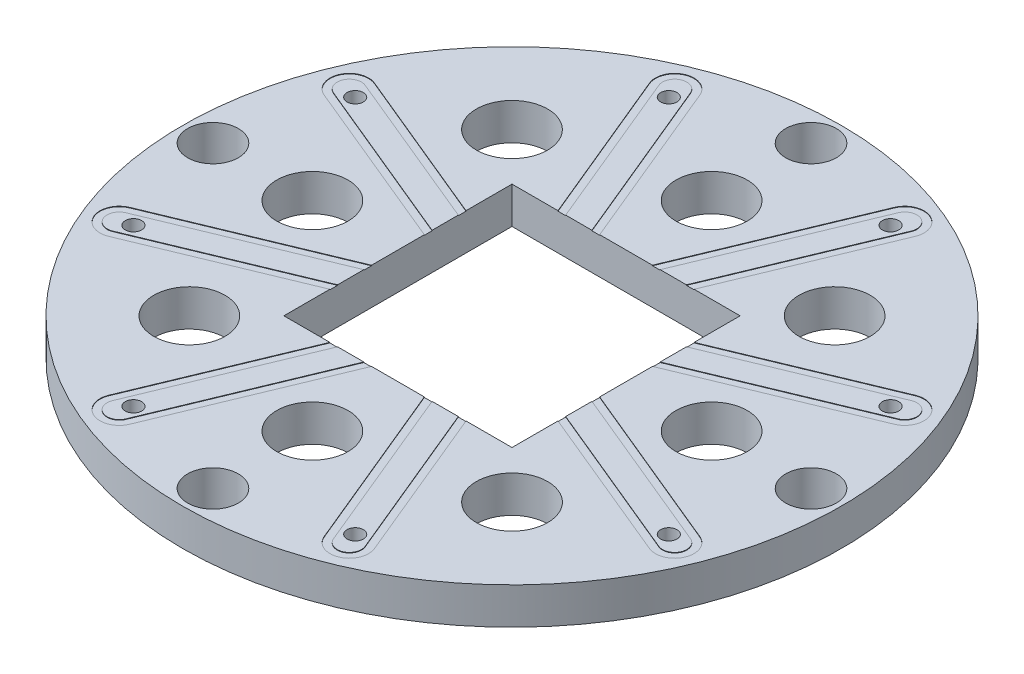
SolidWorks part; units mm, degrees
material "Ceramic Porcelain"
ref_plane "Front Plane" through (0, 0, 0) normal (0, 0, 1) x (1, 0, 0)
ref_plane "Top Plane" through (0, 0, 0) normal (0, 1, 0) x (1, 0, 0)
ref_plane "Right Plane" through (0, 0, 0) normal (1, 0, 0) x (0, 0, -1)
ref_axis "Y Axis" through (0, 0.0762, 0) along (0, -1, 0)
sketch "Boday Sketch" plane through (0, 0, 0) normal (0, 1, 0) x (1, 0, 0)
  circle A0 centre (0, 0) radius 11.557
  dimension "D1" = 23.114
extrude "Body" add sketch "Boday Sketch" against normal blind 1.27
sketch "Copper Sketch" plane through (0, 0, 0) normal (0, 1, 0) x (1, 0, 0)
  circle A0 centre (0, 0) radius 11.557
  dimension "D1" = 23.114
extrude "Copper" add sketch "Copper Sketch" along normal blind 0.0175
sketch "Screw Position" plane through (0, 0, 0) normal (0, 1, 0) x (1, 0, 0)
  point P0 (0, 10.541)
  dimension "D1" = 10.541
sketch "IO Hole Positions" plane through (0, 0, 0) normal (0, 1, 0) x (1, 0, 0)
  point P0 (-3.8881, 9.3866)
  point P1 (3.8881, 9.3866)
  point P5 (9.3866, 3.8881)
  point P6 (9.3866, -3.8881)
  point P7 (3.8881, -9.3866)
  point P8 (-3.8881, -9.3866)
  point P9 (-9.3866, -3.8881)
  point P10 (-9.3866, 3.8881)
  point P11 (0, 0)
  dimension "D2" = 8
sketch "Gap" plane through (0, 0, 0) normal (0, 1, 0) x (1, 0, 0)
  line L1 (0.6236, 0.2583) -> (-3.4102, 9.9969)
  line L2 (-4.6575, 9.4803) -> (-0.6236, -0.2583)
  line L3 (-0.6236, -0.2583) -> (0.6236, 0.2583)
  arc A0 (-3.4102, 9.9969) -> (-4.6575, 9.4803) centre (-4.0339, 9.7386) ccw
  point P0 (0.6236, 0.2583)
sketch "Center Sketch" plane through (0, 0, 0) normal (0, 1, 0) x (1, 0, 0)
  line L0 (0.3926, 0.1626) -> (-3.6412, 9.9013)
  line L1 (-4.4265, 9.576) -> (-0.3926, -0.1626)
  line L2 (-0.3926, -0.1626) -> (0.3926, 0.1626)
  arc A0 (-3.6412, 9.9013) -> (-4.4265, 9.576) centre (-4.0339, 9.7386) ccw
  point P0 (0.3926, 0.1626)
  point P3 (-3.6412, 9.9013)
  dimension "D1" = 0.425
hole_wizard "#0 Clearance Hole1" positions "Sketch23" profile "Sketch24" hole size "#0" standard "ANSI Inch" end condition through all
sketch "Sketch23" plane through (0, 0.0175, 0) normal (0, 1, 0) x (-1, 0, 0)
  point P0 (0, -10.4865)
sketch "Sketch24" plane through (0, 0.0175, -10.4865) normal (1, 0, 0) x (0, 0, 1)
  line L0 (0, 0) -> (0, 1.2875)
  line L1 (0, 1.2875) -> (0.889, 1.2875)
  line L2 (0.889, 1.2875) -> (0.889, 0)
  line L5 (0.889, 0) -> (0, 0)
  line L11 (0, -6.35) -> (0, 107.95) construction
  dimension "Thru Hole Dia." = 1.778
  dimension "Thru Hole Depth" = 1.2875
pattern_circular "Screw Holes" count 4 over 360 about axis through (0, 0.0762, 0) along (0, -1, 0) of "#0 Clearance Hole1"
extrude "Gap Cut" cut sketch "Gap" along normal through all
extrude "Center" add sketch "Center Sketch" along normal blind 0.0175 separate body
sketch "IO Hole Sketch" plane through (0, 0, 0) normal (0, 1, 0) x (1, 0, 0)
  circle A0 centre (-3.8881, 9.3866) radius 0.287
  dimension "D1" = 0.574
extrude "IO Hole" cut sketch "IO Hole Sketch" against normal through all and the other way through all
pattern_circular "Gap Cuts" count 8 over 360 about axis through (0, 0.0762, 0) along (0, -1, 0) of "Gap Cut"
pattern_circular "Centers" count 8 over 360 about axis through (0, 0.0762, 0) along (0, -1, 0) of "Center"
pattern_circular "IO Holes" count 8 over 360 about axis through (0, 0.0762, 0) along (0, -1, 0) of "IO Hole"
sketch "Pocket Sketch" plane through (0, 0, 0) normal (0, 1, 0) x (1, 0, 0)
  line L1 (-4, -4) -> (4, -4)
  line L2 (-4, -4) -> (-4, 4)
  line L3 (-4, 4) -> (4, 4)
  line L4 (4, -4) -> (4, 4)
  line L5 (-4, -4) -> (4, 4) construction
  line L6 (-4, 4) -> (4, -4) construction
  point P0 (0, 0)
  dimension "D2" = 8
  dimension "D1" = 8
extrude "Pocket" cut sketch "Pocket Sketch" against normal through all and the other way through all
sketch "Posts" plane through (0, 0, 0) normal (0, 1, 0) x (1, 0, 0)
  circle A0 centre (0, 7) radius 1.25
  circle A8 centre (-5.6569, 5.6569) radius 1.25
  point P0 (0, 7)
  point P4 (-5.6569, 5.6569)
  dimension "D2" = 2.5
  dimension "D4" = 2.5
  dimension "D1" = 7
  dimension "D3" = 8
extrude "Post Cut" cut sketch "Posts" against normal through all and the other way through all
pattern_circular "Post Cuts" count 4 over 360 about axis through (0, 0.0762, 0) along (0, -1, 0) of "Post Cut"
equation "\"mount_d\"= 0.91in"
equation "\"dieletric_h\"= 0.05in"
equation "\"D1@Boday Sketch\" = \"mount_d\""
equation "\"D1@Body\" = \"dieletric_h\""
equation "\"screw_inner_r\"= 0.415in"
equation "\"io_r\"= 0.4in"
equation "\"D1@Screw Position\" = \"screw_inner_r\""
equation "\"D1@IO Hole Positions\" = \"io_r\""
equation "\"io_hole_d\"= 0.574mm"
equation "\"D1@IO Hole Sketch\" = \"io_hole_d\""
equation "\"W\"= 0.85mm"
equation "\"G\"= 0.25mm"
equation "\"copper_t\"= 17.5um"
equation "\"D1@Gap\"=\"W\" / 2 + \"G\""
equation "\"silicon_size\"= 8mm"
equation "\"D1@Center\" = \"copper_t\""
equation "\"D1@Copper\"=\"copper_t\""
equation "\"D1@Pocket Sketch\" = \"silicon_size\""
equation "\"D2@Pocket Sketch\" = \"silicon_size\""
equation "\"post_r1\"= 7mm"
equation "\"post_r2\" = 8mm"
equation "\"D1@Posts\"=\"post_r1\""
equation "\"post_size\" = 2.5mm"
equation "\"D2@Posts\"=\"post_size\""
equation "\"D3@Posts\"=\"post_r2\""
equation "\"D4@Posts\"=\"post_size\""
